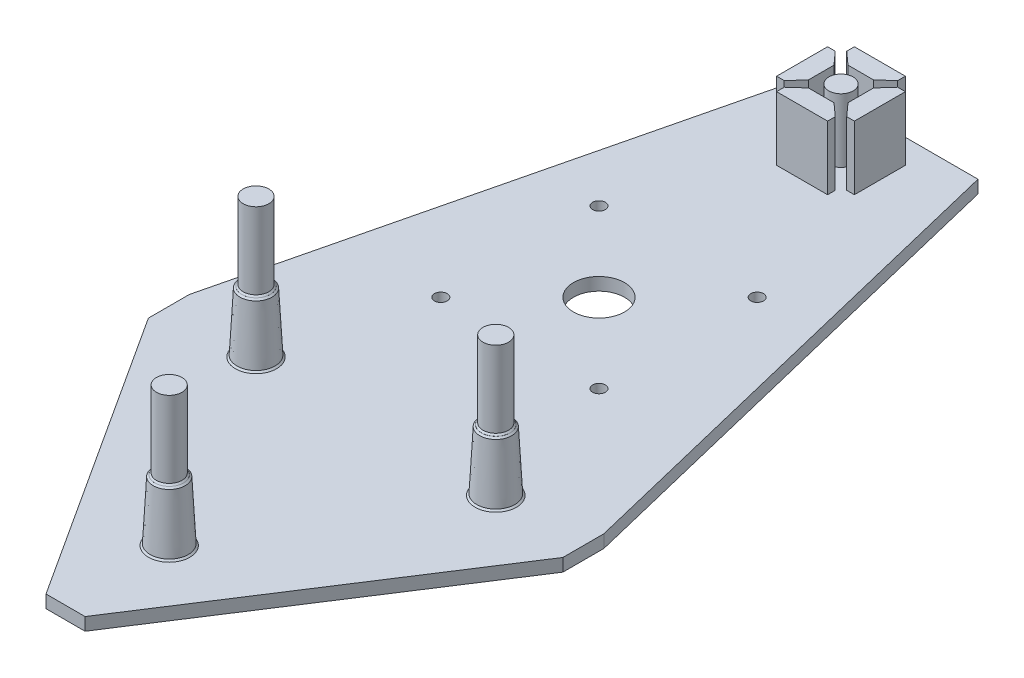
SolidWorks part; units mm, degrees
note: The reader was unsure of these and kept them because the rebuilt part matched: shared geometry of "Sketch7<3>".
ref_plane "Front Plane" through (0, 0, 0) normal (0, 0, 1) x (1, 0, 0)
ref_plane "Top Plane" through (0, 0, 0) normal (0, 1, 0) x (1, 0, 0)
ref_plane "Right Plane" through (0, 0, 0) normal (1, 0, 0) x (0, 0, -1)
sketch "Sketch1" plane through (0, 0, 0) normal (0, 1, 0) x (1, 0, 0)
  line L0 (62.103, -37.272) -> (62.103, -42.352)
  line L1 (0, 0) -> (82.55, 0)
  line L2 (0, 0) -> (0, -164.338)
  line L3 (0, -164.338) -> (82.55, -164.338)
  line L4 (82.55, 0) -> (82.55, -164.338)
  line L5 (62.103, -58.1) -> (62.103, -37.272)
  line L6 (62.103, -42.352) -> (57.023, -42.352)
  line L9 (51.275, 0) -> (31.275, 0)
  line L11 (62.103, -37.272) -> (20.447, -37.272)
  line L12 (62.103, -37.272) -> (62.103, -78.928)
  line L13 (62.103, -78.928) -> (20.447, -78.928)
  line L14 (20.447, -37.272) -> (20.447, -78.928)
  line L15 (41.275, -58.1) -> (82.55, -58.1)
  line L16 (41.275, -58.1) -> (41.275, -37.272)
  line L17 (41.275, -58.1) -> (20.447, -58.1)
  circle A7 centre (41.275, -58.1) radius 5.08
  circle A11 centre (57.023, -42.352) radius 1.27
  circle A15 centre (57.023, -73.848) radius 1.27
  circle A16 centre (25.527, -73.848) radius 1.27
  circle A17 centre (25.527, -42.352) radius 1.27
  point P26 (39.8836, -58.1)
  point P30 (41.275, -58.1)
  dimension "D4" = 5.08
  dimension "D6" = 41.275
  dimension "D9" = 20.828
  dimension "D3" = 5.08
  dimension "D5" = 4
  dimension "D1" = 82.55
  dimension "D2" = 164.338
  dimension "D7" = 41.656
  dimension "D8" = 20.828
extrude "base extrude" add sketch "Sketch1" along normal blind 2.54
sketch "Sketch6" plane through (0, 2.54, 0) normal (0, 1, 0) x (1, 0, 0)
  line L0 (46.355, -16.129) -> (43.815, -13.843)
  line L1 (0, 0) -> (82.55, 0) construction
  line L2 (41.275, -17.653) -> (46.355, -17.653)
  line L3 (45.212, -9.906) -> (45.212, -7.366)
  line L4 (45.212, -9.906) -> (45.212, -12.446)
  line L5 (46.355, -17.653) -> (46.355, -16.129)
  line L6 (49.022, -9.906) -> (49.022, -4.826)
  line L7 (49.022, -9.906) -> (49.022, -14.986)
  line L8 (49.022, -4.826) -> (47.498, -4.826)
  line L9 (47.498, -4.826) -> (45.212, -7.366)
  line L10 (49.022, -14.986) -> (47.498, -14.986)
  line L11 (47.498, -14.986) -> (45.212, -12.446)
  line L12 (41.275, 0) -> (51.181, 0)
  line L13 (41.275, -13.843) -> (43.815, -13.843)
  line L14 (51.181, 0) -> (31.369, 0)
  line L15 (51.181, 0) -> (51.181, -19.812)
  line L16 (51.181, -19.812) -> (31.369, -19.812)
  line L17 (31.369, 0) -> (31.369, -19.812)
  line L18 (41.275, -13.843) -> (38.735, -13.843)
  line L19 (36.195, -16.129) -> (38.735, -13.843)
  line L20 (36.195, -17.653) -> (36.195, -16.129)
  line L21 (41.275, -17.653) -> (36.195, -17.653)
  line L22 (35.052, -14.986) -> (37.338, -12.446)
  line L23 (33.528, -9.906) -> (33.528, -14.986)
  line L24 (33.528, -14.986) -> (35.052, -14.986)
  line L25 (37.338, -9.906) -> (37.338, -12.446)
  line L26 (37.338, -9.906) -> (37.338, -7.366)
  line L27 (35.052, -4.826) -> (37.338, -7.366)
  line L28 (33.528, -4.826) -> (35.052, -4.826)
  line L29 (33.528, -9.906) -> (33.528, -4.826)
  line L30 (36.195, -3.683) -> (38.735, -5.969)
  line L31 (41.275, -2.159) -> (36.195, -2.159)
  line L32 (36.195, -2.159) -> (36.195, -3.683)
  line L33 (41.275, -5.969) -> (38.735, -5.969)
  line L34 (41.275, -5.969) -> (43.815, -5.969)
  line L35 (46.355, -3.683) -> (43.815, -5.969)
  line L36 (46.355, -2.159) -> (46.355, -3.683)
  line L37 (41.275, -2.159) -> (46.355, -2.159)
  circle A0 centre (41.275, -9.906) radius 2.413
  point P44 (41.275, -9.906)
  dimension "D1" = 4
extrude "middle bar holder" add sketch "Sketch6" along normal blind 12.7 contours L29 L23 L24 L22 L25 L26 L27 L28 | A0 | L37 L31 L32 L30 L33 L34 L35 L36 | L11 L10 L7 L6 L8 L9 L3 L4 | L21 L2 L5 L0 L13 L18 L19 L20
sketch "Sketch7" plane through (0, 2.54, 0) normal (0, 1, 0) x (1, 0, 0)
  line L7 (17.399, -114.554) -> (65.151, -114.554)
  circle A0 centre (41.275, -143.692) radius 11.938
  circle A1 centre (41.275, -143.692) radius 2.55
  circle A2 centre (65.151, -102.529) radius 12.025
  circle A3 centre (17.399, -102.529) radius 12.025
  circle A4 centre (65.151, -102.529) radius 2.55
  circle A5 centre (17.399, -102.529) radius 2.55
  circle A6 centre (41.275, -143.692) radius 3.81
  circle A7 centre (65.151, -102.529) radius 3.81
  circle A8 centre (17.399, -102.529) radius 3.81
  dimension "D2" = 9.388
  dimension "D1" = 1.26
  dimension "D3" = 17.2
  dimension "D6" = 47.752
extrude "Boss-Extrude6" add sketch "Sketch7" along normal blind 27.686 contours A5 | A1 | A4
extrude "Boss-Extrude7" add sketch "Sketch7<3>" along normal blind 12.192 contours A6 A1 | A7 A4 | A8 A5
sketch "Sketch7<3>" plane through (0, 2.54, 0) normal (0, 1, 0) x (1, 0, 0) same geometry as "Sketch7"
sketch "Sketch8" plane through (0, 2.54, 0) normal (0, 1, 0) x (1, 0, 0)
  line L0 (45.1655, -164.338) -> (82.55, -106.5667)
  line L1 (82.55, 0) -> (58.655, 0)
  line L2 (82.55, 0) -> (82.55, -98.4064)
  line L3 (82.55, -98.4064) -> (58.655, -98.4064)
  line L4 (58.655, 0) -> (58.655, -98.4064)
  line L5 (82.55, -164.338) -> (45.1655, -164.338)
  line L6 (82.55, -164.338) -> (82.55, -106.5667)
  line L7 (82.55, -106.5667) -> (45.1655, -106.5667)
  line L8 (45.1655, -164.338) -> (45.1655, -106.5667)
  line L9 (82.55, -98.4064) -> (58.655, 0)
  line L10 (41.275, -63.18) -> (41.275, -139.882)
  line L11 (37.3845, -164.338) -> (0, -106.5667)
  line L12 (0, -98.4064) -> (23.895, 0)
  circle A0 centre (41.275, -58.1) radius 5.08 construction
  circle A1 centre (41.275, -143.692) radius 3.81 construction
  line M33 (0, -164.338) -> (82.55, -164.338)
  line M34 (82.55, -164.338) -> (82.55, 0)
  line M35 (82.55, 0) -> (0, 0)
  line M36 (0, 0) -> (0, -164.338)
extrude "Cut-Extrude1" cut sketch "Sketch8" against normal blind 10 contours L11 M33 M36 | L0 M33 M34 | L9 M34 M35 | L12 M36 M35
draft "Draft4" type of draft neutral plane draft angle 4 faces to draft 3 face at (41.275, 14.732, 147.502) face at (17.399, 14.732, 106.339) face at (65.151, 14.732, 106.339) neutral plane through (0, 2.54, 0) neutral plane normal (0, 1, 0) parameters "D1"=4
draft "Draft5" type of draft neutral plane draft angle 3 faces to draft 3 face at (41.275, 14.732, 146.6495) face at (65.151, 14.732, 105.4865) face at (17.399, 14.732, 105.4865) neutral plane through (0, 2.54, 0) neutral plane normal (0, 1, 0) parameters "D1"=3
chamfer "Chamfer1" distance 0.3 angle 45 3 edges at (65.151, 2.54, 106.339) (65.151, 14.732, 105.7) (65.151, 14.732, 105.079)
chamfer "Chamfer2" distance 0.3 angle 45 3 edges at (17.399, 14.732, 105.079) (17.399, 2.54, 106.339) (17.399, 14.732, 105.7)
chamfer "Chamfer3" distance 0.3 angle 45 3 edges at (41.275, 14.732, 146.242) (41.275, 2.54, 147.502) (41.275, 14.732, 146.863)
